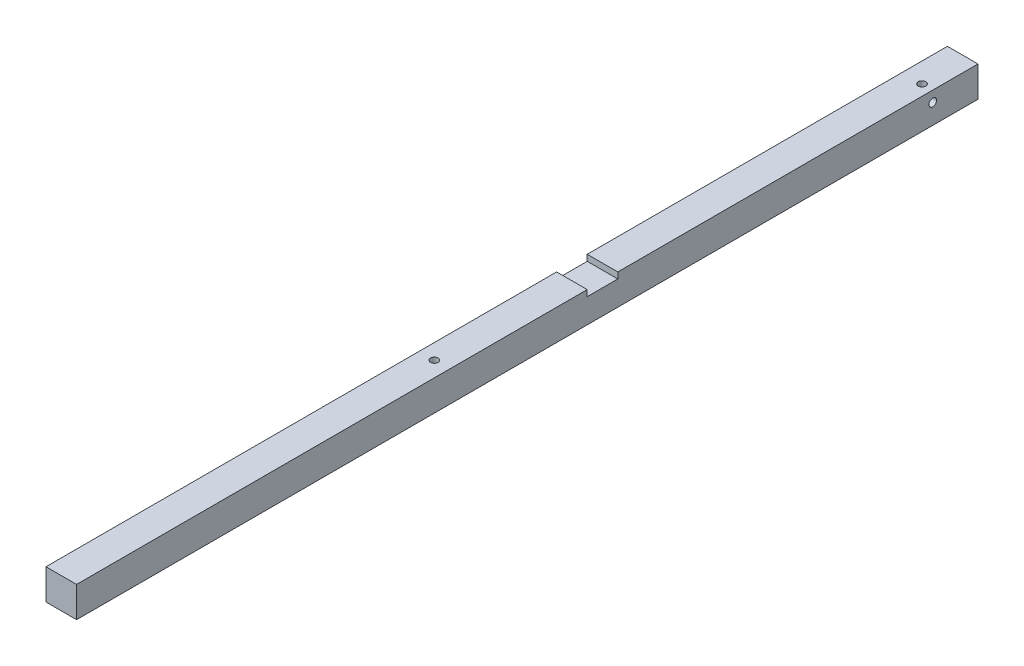
SolidWorks part; units mm, degrees
ref_plane "Plan de face" through (0, 0, 0) normal (0, 0, 1) x (1, 0, 0)
ref_plane "Plan de dessus" through (0, 0, 0) normal (0, 1, 0) x (1, 0, 0)
ref_plane "Plan de droite" through (0, 0, 0) normal (1, 0, 0) x (0, 0, -1)
sketch "Esquisse1" plane through (0, 0, 0) normal (0, 0, 1) x (1, 0, 0)
  line L0 (-5, 5) -> (5, -5) construction
  line L1 (-5, 5) -> (5, 5)
  line L2 (-5, 5) -> (-5, -5)
  line L3 (-5, -5) -> (5, -5)
  line L4 (5, 5) -> (5, -5)
  dimension "D1" = 10
extrude "Boss.-Extru.1" add sketch "Esquisse1" along normal offset from surface (294.8 mm away) 2 offset beyond the face yes
hole_wizard "Trou taraudé M3x0.51" positions "Esquisse3" profile "Esquisse2" tap size "M3x0.5" standard "Ansi Metric"
sketch "Esquisse3" plane through (0, 0, 0) normal (0, 0, -1) x (-1, 0, 0)
  point P0 (0, 0)
sketch "Esquisse2" plane through (0, 0, 0) normal (1, 0, 0) x (0, 1, 0)
  line L0 (0, 0) -> (0, 9.2511)
  line L1 (0, 9.2511) -> (1.25, 8.5)
  line L2 (1.25, 8.5) -> (1.25, 0.275)
  line L3 (1.25, 0.275) -> (1.525, 0)
  line L5 (1.525, 0) -> (0, 0)
  line L6 (-1.25, 0.275) -> (-1.525, 0) construction
  line L10 (0, 9.2511) -> (-1.25, 8.5) construction
  line L11 (0, -6.35) -> (0, 107.95) construction
  dimension "Diamètre du trou pour taraudage" = 2.5
  dimension "Profondeur du trou pour taraudage" = 8.5
  dimension "Diamètre du fraisage entrant" = 3.05
  dimension "Angle du fraisage entrant" = 90
  dimension "Angle de pointe" = 118
cosmetic thread "Filetage de perçage1" parameters "D1"=6, "D2"=3
sketch "Esquisse4" plane through (-5, 0, 0) normal (-1, 0, 0) x (0, 0, 1)
  line L0 (127.8, 3) -> (127.8, 239) construction
  line L1 (127.8, 3) -> (117.8, 3)
  line L2 (127.8, 3) -> (127.8, 5)
  line L3 (127.8, 5) -> (117.8, 5)
  line L4 (117.8, 3) -> (117.8, 5)
  line L5 (117.8, 3) -> (117.8, 239) construction
  line L6 (294.8, 5) -> (0, 5) construction
  dimension "D1" = 2
extrude "Enlèv. mat.-Extru.1" cut sketch "Esquisse4" against normal through all
sketch "Esquisse5" [suppressed] plane through (0, 5, 0) normal (0, 1, 0) x (1, 0, 0)
  line L0 (5, -294.8) -> (5, -127.8) construction
  line L1 (-5, 0) -> (5, 0)
  line L2 (-5, 0) -> (-5, -53.6)
  line L3 (-5, -53.6) -> (5, -53.6)
  line L4 (5, 0) -> (5, -53.6)
  line L5 (5, -117.8) -> (5, 0) construction
  line L6 (5, -53.6) -> (-5, -53.6) construction
hole_wizard "Trou taraudé M3x0.52" positions "Esquisse8" profile "Esquisse7" tap size "M3x0.5" standard "Ansi Metric" end condition through all
sketch "Esquisse8" plane through (0, -5, 0) normal (0, -1, 0) x (-1, 0, 0)
  point P0 (-1.5, -14.8)
sketch "Esquisse7" plane through (1.5, -5, 14.8) normal (1, 0, 0) x (0, 0, -1)
  line L0 (0, 0) -> (0, 10)
  line L1 (0, 10) -> (1.25, 10)
  line L2 (1.25, 10) -> (1.25, 0.275)
  line L3 (1.25, 0.275) -> (1.525, 0)
  line L5 (1.525, 0) -> (0, 0)
  line L6 (-1.25, 0.275) -> (-1.525, 0) construction
  line L11 (0, -6.35) -> (0, 107.95) construction
  dimension "Diamètre du trou pour taraudage jusqu'au prochain" = 2.5
  dimension "Profondeur du trou pour taraudage jusqu'au prochain" = 10
  dimension "Diamètre du fraisage entrant" = 3.05
  dimension "Angle du fraisage entrant" = 90
cosmetic thread "Filetage de perçage2" parameters "D2"=3
hole_wizard "Trou taraudé M3x0.53" positions "Esquisse10" profile "Esquisse9" tap size "M3x0.5" standard "Ansi Metric" end condition through all
sketch "Esquisse10" plane through (-5, 0, 0) normal (-1, 0, 0) x (0, 0, 1)
  point P0 (14.8, 1.5)
sketch "Esquisse9" plane through (-5, 1.5, 14.8) normal (0, 1, 0) x (0, 0, 1)
  line L0 (0, 0) -> (0, 10)
  line L1 (0, 10) -> (1.25, 10)
  line L2 (1.25, 10) -> (1.25, 0.275)
  line L3 (1.25, 0.275) -> (1.525, 0)
  line L5 (1.525, 0) -> (0, 0)
  line L6 (-1.25, 0.275) -> (-1.525, 0) construction
  line L11 (0, -6.35) -> (0, 107.95) construction
  dimension "Diamètre du trou pour taraudage jusqu'au prochain" = 2.5
  dimension "Profondeur du trou pour taraudage jusqu'au prochain" = 10
  dimension "Diamètre du fraisage entrant" = 3.05
  dimension "Angle du fraisage entrant" = 90
cosmetic thread "Filetage de perçage3" parameters "D2"=3
extrude "Enlèv. mat.-Extru.2" [suppressed] cut sketch "Esquisse5" against normal through all
hole_wizard "Trou taraudé M3x0.54" positions "Esquisse12" profile "Esquisse11" tap size "M3x0.5" standard "Ansi Metric" end condition through all
sketch "Esquisse12" plane through (0, -5, 0) normal (0, -1, 0) x (-1, 0, 0)
  point P0 (0, -172.8)
sketch "Esquisse11" plane through (0, -5, 172.8) normal (1, 0, 0) x (0, 0, -1)
  line L0 (0, 0) -> (0, 10)
  line L1 (0, 10) -> (1.25, 10)
  line L2 (1.25, 10) -> (1.25, 0.275)
  line L3 (1.25, 0.275) -> (1.525, 0)
  line L5 (1.525, 0) -> (0, 0)
  line L6 (-1.25, 0.275) -> (-1.525, 0) construction
  line L11 (0, -6.35) -> (0, 107.95) construction
  dimension "Diamètre du trou pour taraudage jusqu'au prochain" = 2.5
  dimension "Profondeur du trou pour taraudage jusqu'au prochain" = 10
  dimension "Diamètre du fraisage entrant" = 3.05
  dimension "Angle du fraisage entrant" = 90
cosmetic thread "Filetage de perçage4" parameters "D2"=3
